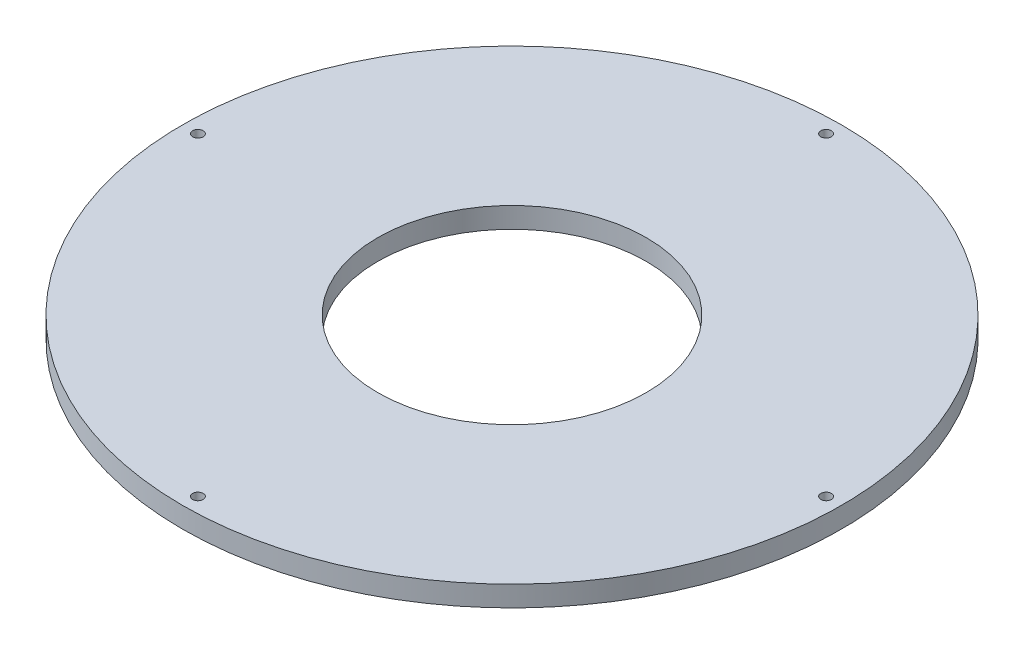
SolidWorks part; units mm, degrees
material "Acrylic (Medium-high impact)"
ref_plane "Front Plane" through (0, 0, 0) normal (0, 0, 1) x (1, 0, 0)
ref_plane "Top Plane" through (0, 0, 0) normal (0, 1, 0) x (1, 0, 0)
ref_plane "Right Plane" through (0, 0, 0) normal (1, 0, 0) x (0, 0, -1)
sketch "Sketch1" plane through (0, 0, 0) normal (0, 1, 0) x (1, 0, 0)
  circle A0 centre (0, 0) radius 41.402
  circle A1 centre (0, 0) radius 101.6
  dimension "D1" = 82.804
  dimension "D2" = 203.2
extrude "Boss-Extrude1" add sketch "Sketch1" along normal blind 6.35
hole_wizard "#4 Clearance Hole1" positions "Sketch2" profile "Sketch3" hole size "#4" standard "ANSI Inch" end condition through all
sketch "Sketch2" plane through (0, 6.35, 0) normal (0, 1, 0) x (1, 0, 0)
  circle A0 centre (0, 0) radius 96.8375
  circle A1 centre (0, 0) radius 101.6 construction
  point P7 (0, 96.8375)
  point P9 (96.8375, 0)
  point P11 (0, -96.8375)
  point P13 (-96.8375, 0)
  dimension "D1" = 4.7625
sketch "Sketch3" plane through (0, 6.35, -96.8375) normal (1, 0, 0) x (0, 0, 1)
  line L0 (0, 0) -> (0, 6.35)
  line L1 (0, 6.35) -> (1.6319, 6.35)
  line L2 (1.6319, 6.35) -> (1.6319, 0)
  line L5 (1.6319, 0) -> (0, 0)
  line L11 (0, -6.35) -> (0, 107.95) construction
  dimension "Thru Hole Dia." = 3.2639
  dimension "Thru Hole Depth" = 6.35
